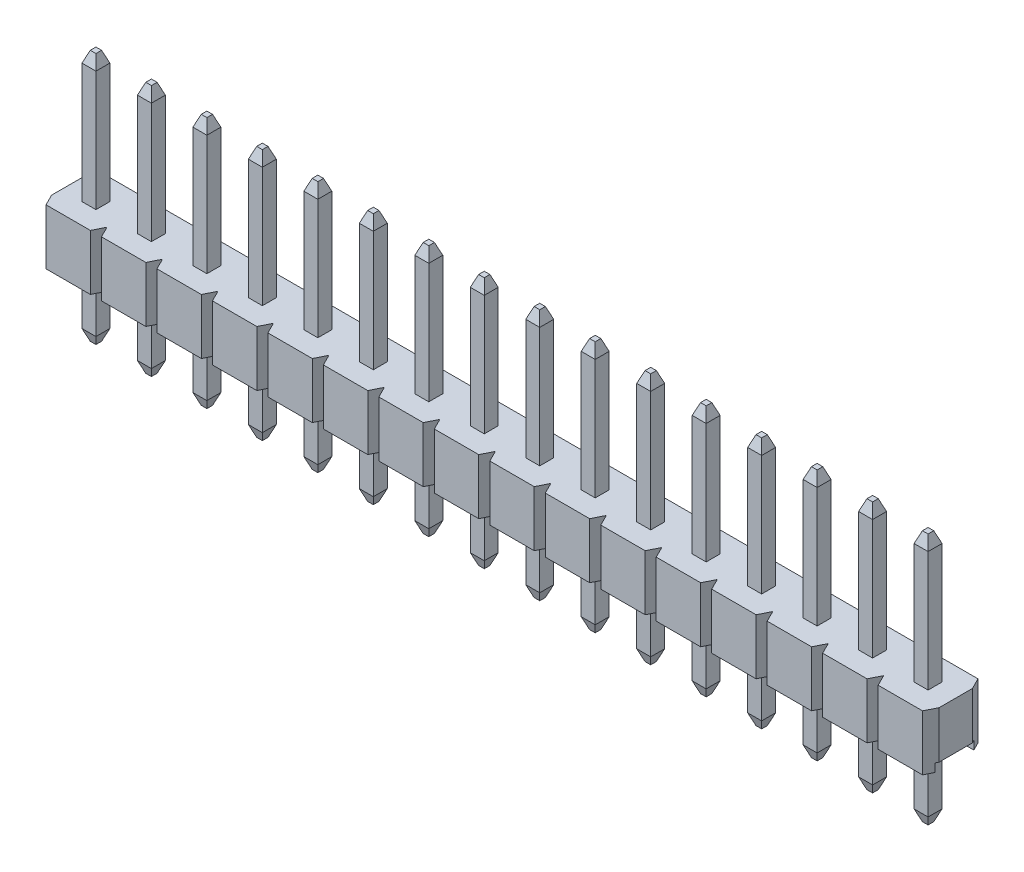
SolidWorks part; units mm, degrees
ref_plane "Front Plane" through (0, 0, 0) normal (0, 0, 1) x (1, 0, 0)
ref_plane "Top Plane" through (0, 0, 0) normal (0, 1, 0) x (1, 0, 0)
ref_plane "Right Plane" through (0, 0, 0) normal (1, 0, 0) x (0, 0, -1)
sketch "Sketch1" plane through (0, 0, 0) normal (0, 1, 0) x (1, 0, 0)
  line L1 (0, 0) -> (2.54, 0)
  line L2 (0, 0) -> (0, 2.54)
  line L3 (0, 2.54) -> (2.54, 2.54)
  line L4 (2.54, 0) -> (2.54, 2.54)
  dimension "D1" = 2.54
  dimension "D2" = 2.54
extrude "Main Body" add sketch "Sketch1" along normal blind 2.54
sketch "Sketch3" plane through (0, 0, 0) normal (-1, 0, 0) x (0, 0, 1)
  line L0 (-2.54, 0) -> (0, 0) construction
  line L1 (-2.159, 0) -> (-0.381, 0)
  line L2 (-2.159, 0) -> (-2.159, 0.381)
  line L3 (-2.159, 0.381) -> (-0.381, 0.381)
  line L4 (-0.381, 0) -> (-0.381, 0.381)
  line L5 (-2.54, 0) -> (-2.159, 0) construction
  line L6 (-0.381, 0) -> (0, 0) construction
  dimension "D1" = 0.381
extrude "Cut-Extrude1" cut sketch "Sketch3" against normal through all
sketch "Sketch4" plane through (0, 2.54, 0) normal (0, 1, 0) x (1, 0, 0)
  line L0 (0, 2.54) -> (0, 2.032)
  line L1 (0, 2.54) -> (0, 0) construction
  line L2 (0, 2.032) -> (0.254, 2.54)
  line L3 (2.54, 2.54) -> (0, 2.54) construction
  line L4 (0.254, 2.54) -> (0, 2.54)
  line L5 (2.54, 2.54) -> (2.286, 2.54)
  line L6 (2.286, 2.54) -> (2.54, 2.032)
  line L7 (2.54, 0) -> (2.54, 2.54) construction
  line L8 (2.54, 2.032) -> (2.54, 2.54)
  line L9 (2.54, 0) -> (2.286, 0)
  line L10 (0, 0) -> (2.54, 0) construction
  line L11 (2.286, 0) -> (2.54, 0.508)
  line L12 (2.54, 0.508) -> (2.54, 0)
  line L14 (0, 0) -> (0, 0.508)
  line L15 (0, 0.508) -> (0.254, 0)
  line L16 (0.254, 0) -> (0, 0)
  line M1 (0, 2.54) -> (0, 0)
  line M2 (0, 0) -> (2.54, 0)
  line M3 (2.54, 0) -> (2.54, 2.54)
  line M4 (2.54, 2.54) -> (0, 2.54)
  dimension "D1" = 0.254
  dimension "D2" = 0.508
extrude "Cut-Extrude2" cut sketch "Sketch4" against normal through all contours L2 M1 M4 | L6 M4 M3 | L15 M1 M2 | L9 L11 L12
pattern_linear "Body Pattern" count 16 spacing 2.54 along (-1, 0, 0) of "Main Body", "Cut-Extrude1", "Cut-Extrude2"
sketch "Sketch2" plane through (0, 2.54, 0) normal (0, 1, 0) x (1, 0, 0)
  line L0 (1.27, 2.54) -> (1.27, 1.59) construction
  line L1 (0.95, 0.95) -> (1.59, 0.95)
  line L2 (0.95, 0.95) -> (0.95, 1.59)
  line L3 (0.95, 1.59) -> (1.59, 1.59)
  line L4 (1.59, 0.95) -> (1.59, 1.59)
  line L6 (2.286, 2.54) -> (0.254, 2.54) construction
  line L8 (1.27, 0.95) -> (1.27, 0) construction
  line L9 (0.254, 0) -> (2.286, 0) construction
  dimension "D1" = 0.64
extrude "Pin" add sketch "Sketch2" along normal blind 6 and the other way offset from surface (5.54 mm away) 3 other way up to face at (1.27, 0, -0.1905)
chamfer "Chamfer1" distance 0.508 distance2 0.1905 4 edges at (0.95, 8.54, -1.27) (1.27, 8.54, -1.59) (1.59, 8.54, -1.27) (1.27, 8.54, -0.95)
chamfer "Chamfer2" distance 0.1905 distance2 0.508 4 edges at (1.27, -3, -1.59) (1.59, -3, -1.27) (1.27, -3, -0.95) (0.95, -3, -1.27)
pattern_linear "Pin Pattern" count 16 spacing 2.54 along (-1, 0, 0) of "Pin", "Chamfer1", "Chamfer2"
